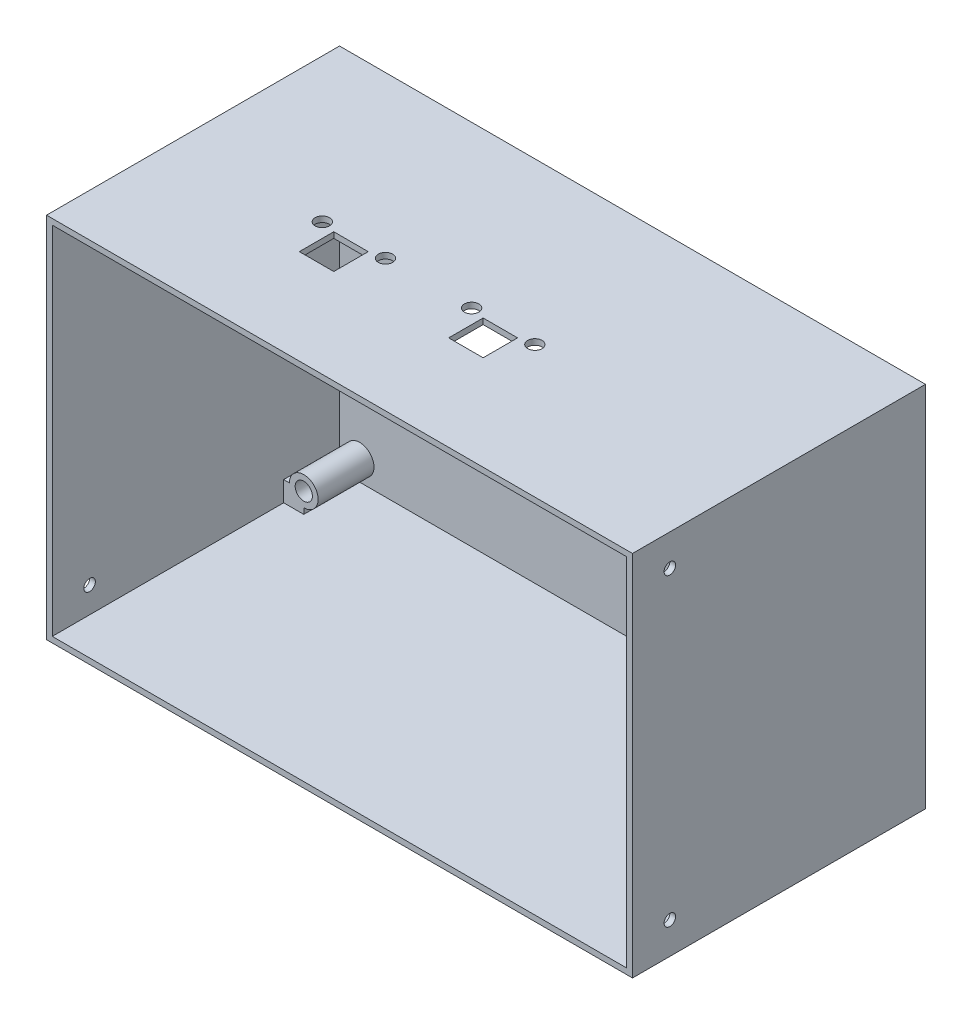
SolidWorks part; units mm, degrees
ref_plane "Спереди" through (0, 0, 0) normal (0, 0, 1) x (1, 0, 0)
ref_plane "Сверху" through (0, 0, 0) normal (0, 1, 0) x (1, 0, 0)
ref_plane "Справа" through (0, 0, 0) normal (1, 0, 0) x (0, 0, -1)
sketch "Эскиз1" plane through (0, 0, 0) normal (0, 0, 1) x (1, 0, 0)
  line L0 (2, 66) -> (2, 2)
  line L1 (2, 2) -> (104, 2)
  line L2 (104, 2) -> (104, 66)
  line L3 (104, 66) -> (2, 66)
  line L13 (3, 65) -> (103, 65)
  line L14 (103, 65) -> (103, 3)
  line L15 (103, 3) -> (3, 3)
  line L16 (3, 3) -> (3, 65)
  line L17 (102, 61.5) -> (103, 61.5)
  line L18 (99.5, 64) -> (99.5, 65)
  line L19 (6.5, 64) -> (6.5, 65)
  line L20 (4, 61.5) -> (3, 61.5)
  line L21 (4, 6.5) -> (3, 6.5)
  line L22 (6.5, 4) -> (6.5, 3)
  line L23 (99.5, 4) -> (99.5, 3)
  line L24 (102, 6.5) -> (103, 6.5)
  line L33 (15, 46.9) -> (91, 46.9)
  line L34 (91, 21.1) -> (15, 21.1)
  line L35 (15, 46.9) -> (15, 21.1)
  line L36 (91, 46.9) -> (91, 21.1)
  circle A0 centre (6.5, 61.5) radius 1.5
  arc A1 (6.5, 64) -> (4, 61.5) centre (6.5, 61.5) cw
  circle A2 centre (99.5, 61.5) radius 1.5
  arc A3 (99.5, 64) -> (102, 61.5) centre (99.5, 61.5) ccw
  circle A4 centre (99.5, 6.5) radius 1.5
  arc A5 (99.5, 4) -> (102, 6.5) centre (99.5, 6.5) cw
  circle A6 centre (6.5, 6.5) radius 1.5
  arc A7 (4, 6.5) -> (6.5, 4) centre (6.5, 6.5) cw
  dimension "D8" = 1
  dimension "D10" = 1
  dimension "D9" = 1
  dimension "D1" = 64
  dimension "D2" = 102
  dimension "D7" = 1
extrude "Бобышка-Вытянуть1" add sketch "Эскиз1" along normal blind 50 contours L0 L1 L2 L14 L15 L16 | L0 L16 L13 L14 L2 L3 region at (53, 65.8796, 0)
extrude "Бобышка-Вытянуть2" add sketch "Эскиз1<3>" along normal blind 9.72 contours A1 L19 L13 L16 L20 A0 | L18 A3 L17 L14 L13 A2 | A5 L23 L15 L14 L24 A4 | A7 L21 L16 L15 L22 A6 region at (4.75, 64.9151, 0) region at (101.25, 64.9151, 0) region at (3.5, 6.4151, 0) region at (102.9151, 4.75, 0)
sketch "Эскиз1<3>" plane through (0, 0, 0) normal (0, 0, 1) x (1, 0, 0) same geometry as "Эскиз1"
sketch "Эскиз4" plane through (0, 66, 0) normal (0, 1, 0) x (1, 0, 0)
  line L0 (2, 0) -> (2, 1)
  line L1 (2, 0) -> (104, 0)
  line L2 (104, 0) -> (104, 1)
  line L3 (2, 1) -> (104, 1)
extrude "Бобышка-Вытянуть3" add sketch "Эскиз4" against normal blind 64
extrude "Вырез-Вытянуть1" cut sketch "Эскиз1<5>" against normal blind 1 contours L36 L33 L35 L34 region at (53, 34, 0)
sketch "Эскиз1<5>" plane through (0, 0, 0) normal (0, 0, 1) x (1, 0, 0) same geometry as "Эскиз1"
sketch "Эскиз5" plane through (103, 0, 0) normal (-1, 0, 0) x (0, 0, 1)
  circle A0 centre (43.5, 7.5) radius 1
  circle A1 centre (43.5, 60.5) radius 1
extrude "Вырез-Вытянуть2" cut sketch "Эскиз5" along normal blind 102 and the other way blind 1
sketch "Эскиз6" plane through (0, 66, 0) normal (0, 1, 0) x (1, 0, 0)
  line L0 (2, -27) -> (27, -27) construction
  line L1 (2, -50) -> (2, 1) construction
  line L2 (27, -27) -> (27, 1) construction
  line L3 (104, 1) -> (2, 1) construction
  line L4 (27, -27) -> (38, -27) construction
  line L5 (32.5, -27) -> (32.5, -34) construction
  line L6 (38, -27) -> (88.8556, -27) construction
  line L7 (29.5, -33.5) -> (35.5, -33.5)
  line L8 (29.5, -33.5) -> (29.5, -27.5)
  line L9 (29.5, -27.5) -> (35.5, -27.5)
  line L10 (35.5, -33.5) -> (35.5, -27.5)
  line L11 (29.5, -33.5) -> (35.5, -27.5) construction
  line L12 (29.5, -27.5) -> (35.5, -33.5) construction
  line L13 (53, -27) -> (64, -27) construction
  line L14 (58.5, -27) -> (58.5, -34) construction
  line L15 (55.5, -33.5) -> (61.5, -33.5)
  line L16 (55.5, -33.5) -> (55.5, -27.5)
  line L17 (55.5, -27.5) -> (61.5, -27.5)
  line L18 (61.5, -33.5) -> (61.5, -27.5)
  line L19 (55.5, -33.5) -> (61.5, -27.5) construction
  line L20 (55.5, -27.5) -> (61.5, -33.5) construction
  circle A0 centre (27, -27) radius 1.25
  circle A1 centre (38, -27) radius 1.25
  circle A2 centre (53, -27) radius 1.25
  circle A3 centre (64, -27) radius 1.25
  point P12 (32.5, -30.5)
  point P14 (32.5, -30.5)
  point P25 (58.5, -30.5)
  point P27 (58.5, -30.5)
  point P31 (0, 0)
  point P32 (53, -27)
  point P33 (0, 0)
  point P34 (0, 0)
  point P35 (0, 0)
  dimension "D1" = 2.5
  dimension "D2" = 2.5
  dimension "D7" = 2.5
  dimension "D8" = 2.5
  dimension "D3" = 11
  dimension "D4" = 3.5
  dimension "D5" = 6
  dimension "D6" = 6
  dimension "D9" = 11
  dimension "D10" = 3.5
  dimension "D11" = 6
  dimension "D12" = 6
  dimension "D13" = 15
  dimension "D14" = 28
  dimension "D15" = 25
extrude "Вырез-Вытянуть3" cut sketch "Эскиз6" against normal blind 10
